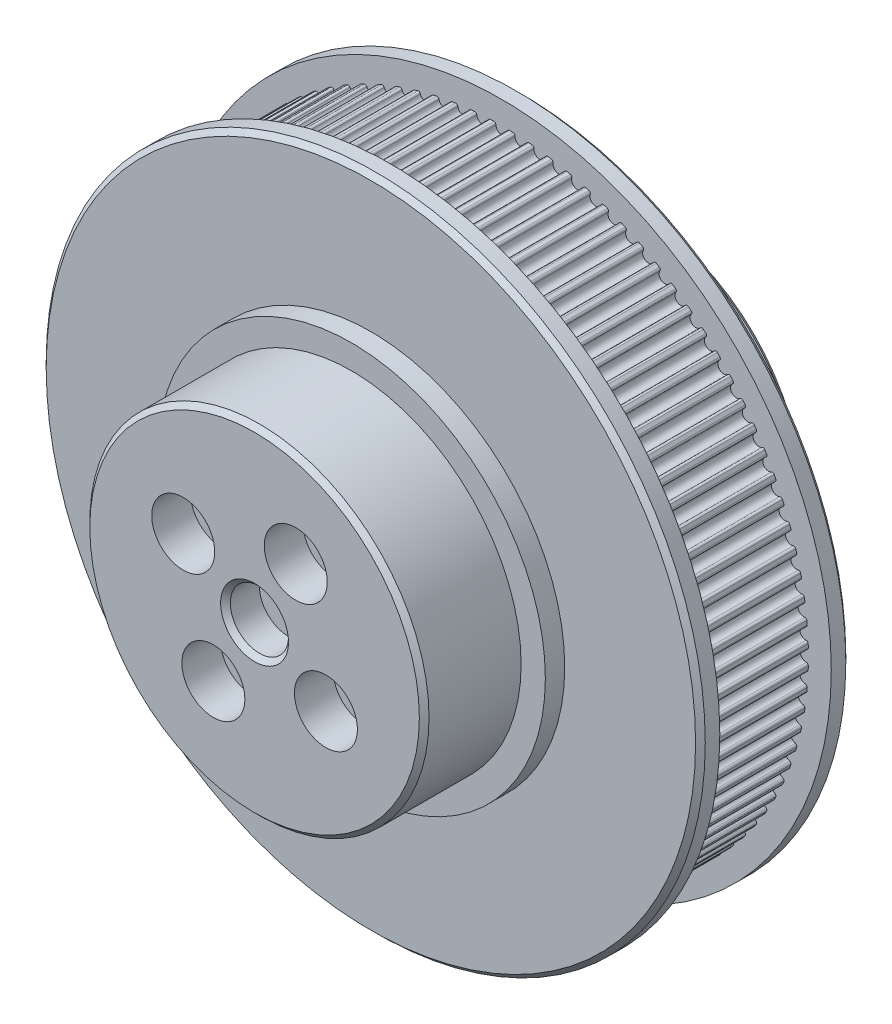
SolidWorks part; units mm, degrees
ref_plane "Спереди" through (0, 0, 0) normal (0, 0, 1) x (1, 0, 0)
ref_plane "Сверху" through (0, 0, 0) normal (0, 1, 0) x (1, 0, 0)
ref_plane "Справа" through (0, 0, 0) normal (1, 0, 0) x (0, 0, -1)
ref_axis "Ось1" through (0, 0, 55) along (0, 0, -1)
sketch "SketchRevolveGearBelt01" plane through (0, 0, 0) normal (1, 0, 0) x (0, 0, -1)
  line L0 (0, 0) -> (11.5, 0)
  line L1 (11.5, 0) -> (11.5, 31.6405)
  line L2 (11.5, 31.6405) -> (0, 31.6405)
  line L3 (0, 31.6405) -> (0, 0)
  dimension "GearBeltOutsideDiameter" = 31.6405
  dimension "D1" = 11.5
revolve "GearBelt01" add sketch "SketchRevolveGearBelt01" angle 360 about L0
sketch "SketchToothGearBelt01" plane through (0, 0, 0) normal (0, 0, 1) x (1, 0, 0)
  line L0 (-0.814, 31.63) -> (0, 34.1805)
  line L1 (0, 34.1805) -> (0.814, 31.63)
  arc A0 (0.814, 31.63) -> (0.6, 31.4215) centre (0.8086, 31.4215) ccw
  arc A1 (0.6, 31.4215) -> (-0.6, 31.4215) centre (0, 31.4215) cw
  arc A2 (-0.6, 31.4215) -> (-0.814, 31.63) centre (-0.8086, 31.4215) ccw
  dimension "GearBeltToothR1" = 0.4172
  dimension "GearBeltToothR2" = 1.2
  dimension "GearBeltToothCapX1" = 0.814
  dimension "GearBeltToothCapY1" = 2.5505
  dimension "GearBeltToothCapX2" = 0.814
  dimension "GearBeltToothCapY2" = 2.5505
extrude "ToothExtrudeCutGearBelt01" cut sketch "SketchToothGearBelt01" against normal blind 11.5
ref_axis "Ось2" through (34.8045, 0, 0) along (-1, 0, 0)
ref_plane "Плоскость1" through (0, 0, 0) normal (0, 0, -1) x (1, 0, 0)
pattern_circular "PatternGearBelt01" count 100 every 3.6 about axis through (0, 0, 55) along (0, 0, -1) of "ToothExtrudeCutGearBelt01"
sketch "Эскиз5" plane through (0, 0, 0) normal (0, 0, -1) x (-1, 0, 0)
  circle A0 centre (0, 0) radius 34
  dimension "D1" = 68
extrude "Бобышка-Вытянуть1" add sketch "Эскиз5" against normal blind 2
sketch "Эскиз20" plane through (0, 0, -11.5) normal (0, 0, -1) x (-1, 0, 0)
  circle A0 centre (0, 0) radius 34
extrude "Бобышка-Вытянуть10" add sketch "Эскиз20" along normal blind 2
sketch "Эскиз12" plane through (0, 0, -13.5) normal (0, 0, -1) x (-1, 0, 0)
  circle A0 centre (0, 0) radius 20
extrude "Бобышка-Вытянуть5" add sketch "Эскиз12" along normal blind 2
sketch "Эскиз6" plane through (0, 0, 2) normal (0, 0, 1) x (1, 0, 0)
  circle A0 centre (0, 0) radius 20
  dimension "D1" = 40
extrude "Бобышка-Вытянуть6" add sketch "Эскиз6" along normal blind 2
sketch "Эскиз13" plane through (0, 0, 4) normal (0, 0, 1) x (1, 0, 0)
  circle A0 centre (0, 0) radius 17.5
  dimension "D1" = 35
extrude "Бобышка-Вытянуть7" add sketch "Эскиз13" along normal blind 10
sketch "Эскиз14" plane through (0, 0, -15.5) normal (0, 0, -1) x (-1, 0, 0)
  circle A0 centre (0, 0) radius 17.5
  dimension "D1" = 35
extrude "Бобышка-Вытянуть8" add sketch "Эскиз14" along normal blind 10
sketch "Эскиз15" plane through (0, 0, -25.5) normal (0, 0, -1) x (-1, 0, 0)
  circle A0 centre (0, 0) radius 12.1
  dimension "D1" = 24.2
extrude "Вырез-Вытянуть1" cut sketch "Эскиз15" against normal blind 7
sketch "Эскиз16" plane through (0, 0, 0) normal (0, 0, 1) x (1, 0, 0)
  line L0 (0, 0) -> (4.25, 7.3612) construction
  line L1 (0, 0) -> (-46.2056, 0) construction
  line L2 (0, 0) -> (7.3612, -4.25) construction
  line L3 (0, 0) -> (-4.25, -7.3612) construction
  line L4 (0, 0) -> (-7.3612, 4.25) construction
  circle A0 centre (0, 0) radius 8.5 construction
  circle A1 centre (4.25, 7.3612) radius 1.75
  circle A2 centre (7.3612, -4.25) radius 1.75
  circle A3 centre (-4.25, -7.3612) radius 1.75
  circle A4 centre (-7.3612, 4.25) radius 1.75
  point P16 (0, 0)
  dimension "D1" = 17
  dimension "D3" = 3.5
  dimension "D2" = 60
  dimension "D4" = 4
extrude "Вырез-Вытянуть2" cut sketch "Эскиз16" against normal through all both and the other way through all
sketch "Эскиз17" plane through (0, 0, 14) normal (0, 0, 1) x (1, 0, 0)
  circle A0 centre (4.25, 7.3612) radius 3.25
  circle A1 centre (7.3612, -4.25) radius 3.25
  circle A2 centre (-4.25, -7.3612) radius 3.25
  circle A3 centre (-7.3612, 4.25) radius 3.25
  point P12 (0, 0)
  dimension "D1" = 4
extrude "Вырез-Вытянуть3" cut sketch "Эскиз17" against normal blind 4
sketch "Эскиз18" plane through (0, 0, 14) normal (0, 0, 1) x (1, 0, 0)
  circle A0 centre (0, 0) radius 3
extrude "Вырез-Вытянуть4" cut sketch "Эскиз18" against normal blind 3.5
sketch "Эскиз19" plane through (0, 0, 0) normal (0, 0, 1) x (1, 0, 0)
  circle A0 centre (0, 0) radius 1
extrude "Вырез-Вытянуть5" cut sketch "Эскиз19" against normal through all both and the other way through all
chamfer "Фаска1" distance 0.5 angle 45 3 edges at (-12.1, 0, -25.5) (-17.5, 0, -25.5) (17.5, 0, 14)
fillet "Скругление1" radius 0.4 1 edges at (-12.1, 0, -18.5)
chamfer "Фаска2" distance 0.5 angle 45 1 edges at (3, 0, 14)
chamfer "Фаска3" distance 0.5 angle 45 2 edges at (-34, 0, -13.5) (-34, 0, 2)
